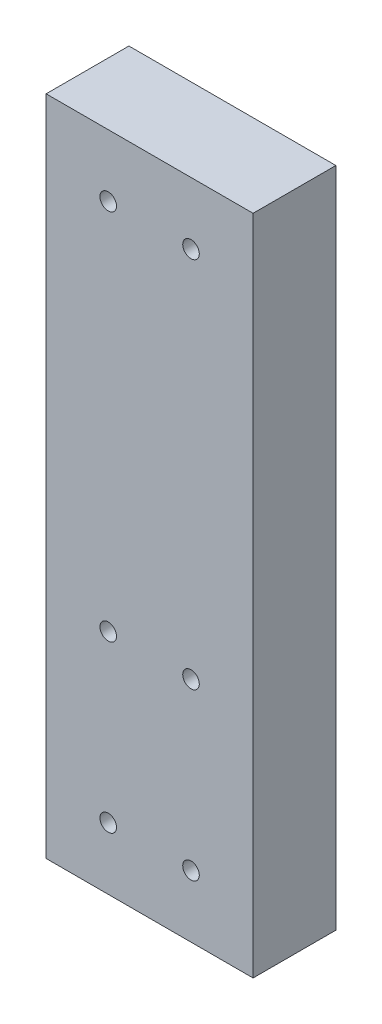
SolidWorks part; units mm, degrees
material "Mahogany"
ref_plane "Plan de face" through (0, 0, 0) normal (0, 0, 1) x (1, 0, 0)
ref_plane "Plan de dessus" through (0, 0, 0) normal (0, 1, 0) x (1, 0, 0)
ref_plane "Plan de droite" through (0, 0, 0) normal (1, 0, 0) x (0, 0, -1)
sketch "Sketch1" plane through (0, 0, 0) normal (0, 0, 1) x (1, 0, 0)
  line L1 (0, 0) -> (25, 0)
  line L2 (0, 0) -> (0, -80)
  line L3 (0, -80) -> (25, -80)
  line L4 (25, 0) -> (25, -80)
  dimension "D1" = 25
  dimension "D2" = 80
extrude "Boss-Extrude1" add sketch "Sketch1" along normal blind 10
sketch "Sketch2" plane through (0, 0, 10) normal (0, 0, 1) x (1, 0, 0)
  line L0 (12.5, 0) -> (12.5, -80) construction
  line L1 (25, 0) -> (0, 0) construction
  line L2 (0, -80) -> (25, -80) construction
  line L3 (0, -7.5) -> (25, -7.5) construction
  line L4 (0, 0) -> (0, -80) construction
  line L5 (25, -80) -> (25, 0) construction
  line L6 (0, -72.5) -> (25, -72.5) construction
  line L7 (0, -52.5) -> (25, -52.5) construction
  line L8 (7.5, 0) -> (7.5, -80) construction
  circle A0 centre (7.5, -7.5) radius 1
  circle A1 centre (7.5, -72.5) radius 1
  circle A2 centre (7.5, -52.5) radius 1
  circle A3 centre (17.5, -72.5) radius 1
  circle A4 centre (17.5, -52.5) radius 1
  circle A5 centre (17.5, -7.5) radius 1
  point P24 (0, 0)
  point P25 (0, 0)
  dimension "D2" = 7.5
  dimension "D3" = 2
  dimension "D4" = 2
  dimension "D8" = 2
  dimension "D1" = 7.5
  dimension "D5" = 5
  dimension "D7" = 52.5
extrude "Cut-Extrude1" cut sketch "Sketch2" against normal through all contours A2 | A1 | A0 | A5 | A4 | A3 region at (7.5, -7.5, 10) region at (7.5, -72.5, 10) region at (7.5, -52.5, 10)
